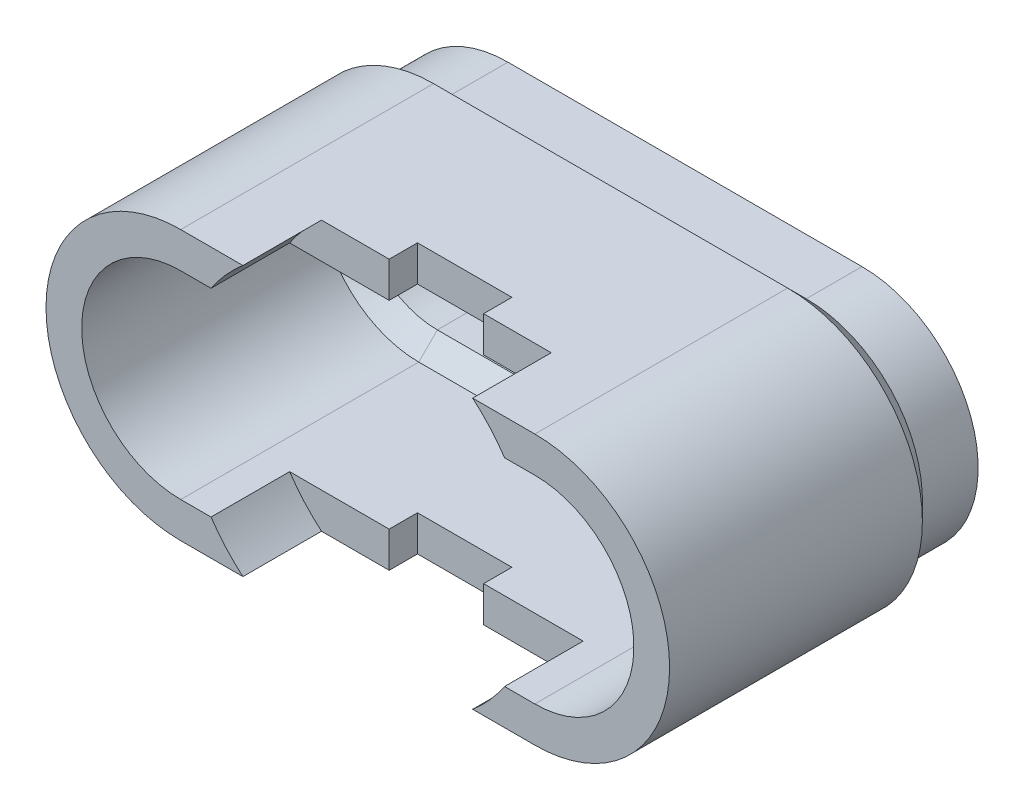
SolidWorks part; units mm, degrees
ref_plane "Front Plane" through (0, 0, 0) normal (0, 0, 1) x (1, 0, 0)
ref_plane "Top Plane" through (0, 0, 0) normal (0, 1, 0) x (1, 0, 0)
ref_plane "Right Plane" through (0, 0, 0) normal (1, 0, 0) x (0, 0, -1)
sketch "Sketch2" plane through (0, 0, 0) normal (0, 0, 1) x (1, 0, 0)
  line L4 (-4.7625, -3.1242) -> (4.7625, -3.1242)
  line L5 (4.7625, 3.1242) -> (-4.7625, 3.1242)
  line L6 (-4.7625, -3.1242) -> (4.7625, -3.1242)
  line L7 (4.7625, 3.1242) -> (-4.7625, 3.1242)
  arc A4 (4.7625, -3.1242) -> (4.7625, 3.1242) centre (4.7625, 0) ccw
  arc A5 (-4.7625, 3.1242) -> (-4.7625, -3.1242) centre (-4.7625, 0) ccw
  arc A6 (4.7625, -3.1242) -> (4.7625, 3.1242) centre (4.7625, 0) ccw
  arc A7 (-4.7625, 3.1242) -> (-4.7625, -3.1242) centre (-4.7625, 0) ccw
  dimension "D1" = 0.0508
extrude "Boss-Extrude1" add sketch "Sketch2" against normal up to surface (1.5 mm away)
extrude "Boss-Extrude3" add sketch "Sketch2<3>" along normal blind 0.5 draft 45 draft outward yes
sketch "Sketch2<3>" plane through (0, 0, 0) normal (0, 0, 1) x (1, 0, 0) same geometry as "Sketch2"
sketch "Sketch3" plane through (0, 0, 0.5) normal (0, 0, 1) x (1, 0, 0)
  line L2 (-4.7625, -3.6242) -> (4.7625, -3.6242)
  line L3 (4.7625, 3.6242) -> (-4.7625, 3.6242)
  line L4 (-4.7625, -3.6242) -> (4.7625, -3.6242)
  line L5 (4.7625, 3.6242) -> (-4.7625, 3.6242)
  arc A2 (-4.7625, 3.6242) -> (-4.7625, -3.6242) centre (-4.7625, 0) ccw
  arc A3 (4.7625, -3.6242) -> (4.7625, 3.6242) centre (4.7625, 0) ccw
  arc A4 (-4.7625, 3.6242) -> (-4.7625, -3.6242) centre (-4.7625, 0) ccw
  arc A5 (4.7625, -3.6242) -> (4.7625, 3.6242) centre (4.7625, 0) ccw
  dimension "D1" = 0
extrude "Boss-Extrude4" add sketch "Sketch3" along normal up to surface (6.8 mm away)
shell "Shell1" thickness 0.96 removed face at (0, 0, 7.3)
sketch "Sketch4" plane through (0, 0, 7.3) normal (0, 0, 1) x (1, 0, 0)
  line L4 (1.3335, 4.572) -> (-1.3335, 4.572)
  line L5 (-4.572, 1.3335) -> (-4.572, -1.3335)
  line L6 (-1.3335, -4.572) -> (1.3335, -4.572)
  line L7 (4.572, -1.3335) -> (4.572, 1.3335)
  line L8 (1.3335, 4.572) -> (-1.3335, 4.572)
  line L9 (-4.572, 1.3335) -> (-4.572, -1.3335)
  line L10 (-1.3335, -4.572) -> (1.3335, -4.572)
  line L11 (4.572, -1.3335) -> (4.572, 1.3335)
  arc A4 (4.572, 1.3335) -> (1.3335, 4.572) centre (0, 0) ccw
  arc A5 (-1.3335, 4.572) -> (-4.572, 1.3335) centre (0, 0) ccw
  arc A6 (-4.572, -1.3335) -> (-1.3335, -4.572) centre (0, 0) ccw
  arc A7 (1.3335, -4.572) -> (4.572, -1.3335) centre (0, 0) ccw
  arc A8 (4.572, 1.3335) -> (1.3335, 4.572) centre (0, 0) ccw
  arc A9 (-1.3335, 4.572) -> (-4.572, 1.3335) centre (0, 0) ccw
  arc A10 (-4.572, -1.3335) -> (-1.3335, -4.572) centre (0, 0) ccw
  arc A11 (1.3335, -4.572) -> (4.572, -1.3335) centre (0, 0) ccw
  dimension "D1" = 0
extrude "Cut-Extrude1" cut sketch "Sketch4" against normal up to surface (2.1141 mm away)
sketch "Sketch5" plane through (0, 0, 5.1859) normal (0, 0, 1) x (1, 0, 0)
  line L0 (-3.0898, 3.6242) -> (3.0898, 3.6242) construction
  line L1 (-1.27, 3.6242) -> (1.27, 3.6242)
  line L2 (-1.27, 3.6242) -> (-1.27, -3.6242)
  line L3 (-1.27, -3.6242) -> (1.27, -3.6242)
  line L4 (1.27, 3.6242) -> (1.27, -3.6242)
  line L5 (3.0898, -3.6242) -> (-3.0898, -3.6242) construction
  line L6 (0, 3.6242) -> (0, 0) construction
  dimension "D1" = 2.54
extrude "Cut-Extrude2" cut sketch "Sketch5" against normal blind 0.762
